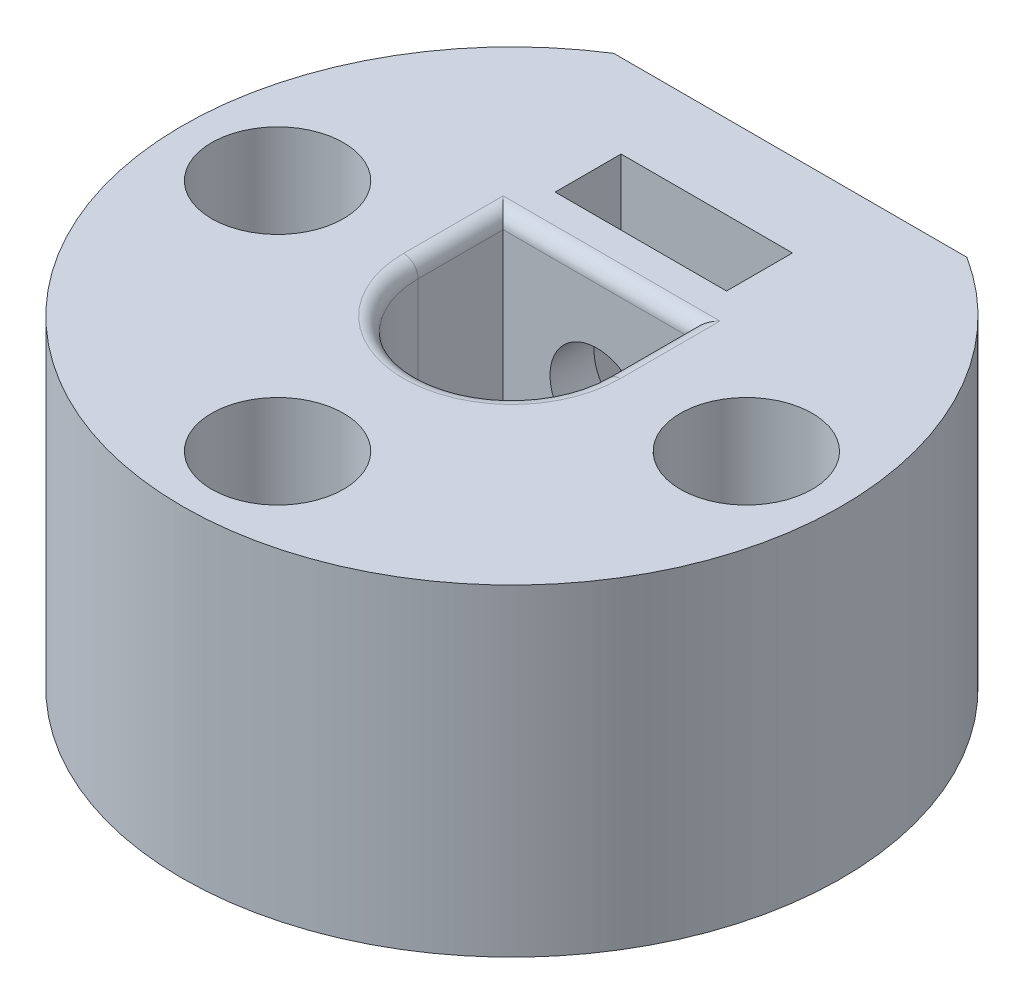
SolidWorks part; units mm, degrees
ref_plane "Plan de face" through (0, 0, 0) normal (0, 0, 1) x (1, 0, 0)
ref_plane "Plan de dessus" through (0, 0, 0) normal (0, 1, 0) x (1, 0, 0)
ref_plane "Plan de droite" through (0, 0, 0) normal (1, 0, 0) x (0, 0, -1)
sketch "Esquisse1" plane through (0, 0, 0) normal (0, 1, 0) x (1, 0, 0)
  line L1 (-3.2, 0) -> (-3.2, 2.9)
  line L2 (3.2, 0) -> (3.2, 2.9)
  line L3 (3.2, 2.9) -> (-3.2, 2.9)
  line L4 (6.026, 9.5) -> (-6.026, 9.5)
  arc A0 (-6.026, 9.5) -> (6.026, 9.5) centre (0, 0) ccw
  arc A1 (-3.2, 0) -> (3.2, 0) centre (0, 0) ccw
  point P10 (0, 2.9)
  dimension "D1" = 22.5
  dimension "D2" = 6.4
  dimension "D3" = 2.9
  dimension "D4" = 9.5
extrude "Boss.-Extru.1" add sketch "Esquisse1" along normal blind 8
fillet "Congé1" radius 0.5 4 edges at (0, 8, 3.2) (-3.2, 8, -1.45) (3.2, 8, -1.45) (0, 8, -2.9)
sketch "Esquisse6" plane through (0, 0, 0) normal (0, 0, 1) x (1, 0, 0)
  line L0 (0, 0) -> (0, 8) construction
  line L1 (11.25, 8) -> (-11.25, 8) construction
  line L2 (11.25, 8) -> (-11.25, 8) construction
  circle A0 centre (0, 4) radius 1.6
  dimension "D1" = 3.2
  dimension "D2" = 4
extrude "Enlèv. mat.-Extru.1" cut sketch "Esquisse6" against normal through all
sketch "Esquisse7" plane through (0, 0, 0) normal (0, 1, 0) x (1, 0, 0)
  line L1 (-2.925, 4.4) -> (2.925, 4.4)
  line L2 (-2.925, 4.4) -> (-2.925, 6.65)
  line L3 (-2.925, 6.65) -> (2.925, 6.65)
  line L4 (2.925, 4.4) -> (2.925, 6.65)
  line L5 (-2.925, 4.4) -> (2.925, 6.65) construction
  line L6 (-2.925, 6.65) -> (2.925, 4.4) construction
  line L7 (3.2, 2.9) -> (-3.2, 2.9) construction
  point P0 (0, 5.525)
  dimension "D3" = 1.5
  dimension "D1" = 2.25
  dimension "D2" = 5.85
extrude "Enlèv. mat.-Extru.2" cut sketch "Esquisse7" along normal through all
sketch "Esquisse8" plane through (0, 0, 0) normal (0, -1, 0) x (1, 0, 0)
  line L0 (-6.026, -9.5) -> (6.026, -9.5)
  line L1 (6.026, -9.5) -> (-6.026, -9.5) construction
  arc A0 (6.026, -9.5) -> (-6.026, -9.5) centre (0, 0) ccw
extrude "Boss.-Extru.2" add sketch "Esquisse8" along normal blind 3
hole_wizard "Chambrage pour vis à tête cylindrique à 6 pans creux (ou vis CHC) M21" positions "Esquisse12" profile "Esquisse13" counterbore size "M2" standard "Ansi Metric" end condition through all
sketch "Esquisse12" plane through (0, 8, 0) normal (0, 1, 0) x (1, 0, 0)
  line L0 (-8, 0) -> (0, 0) construction
  line L1 (0, 0) -> (0, -8) construction
  line L3 (0, 0) -> (8, 0) construction
  point P0 (-8, 0)
  point P2 (0, -8)
  point P4 (8, 0)
  dimension "D1" = 8
sketch "Esquisse13" plane through (-8, 8, 0) normal (1, 0, 0) x (0, 0, 1)
  line L0 (0, 0) -> (0, 11)
  line L1 (0, 11) -> (1.25, 11)
  line L3 (1.25, 11) -> (1.25, 5.3)
  line L4 (1.25, 5.3) -> (2.25, 5.3)
  line L5 (2.25, 5.3) -> (2.25, 0)
  line L7 (2.25, 0) -> (0, 0)
  line L11 (0, -6.35) -> (0, 107.95) construction
  dimension "Diamètre du perçage jusqu'au prochain" = 2.5
  dimension "Profondeur du perçage jusqu'au prochain" = 11
  dimension "Diamètre du chambrage" = 4.5
  dimension "Profondeur du chambrage" = 5.3
sketch "Esquisse14" plane through (0, -3, 0) normal (0, -1, 0) x (1, 0, 0)
  circle A0 centre (0, 0) radius 4.25
  dimension "D1" = 8.5
extrude "Enlèv. mat.-Extru.3" cut sketch "Esquisse14" against normal blind 2
